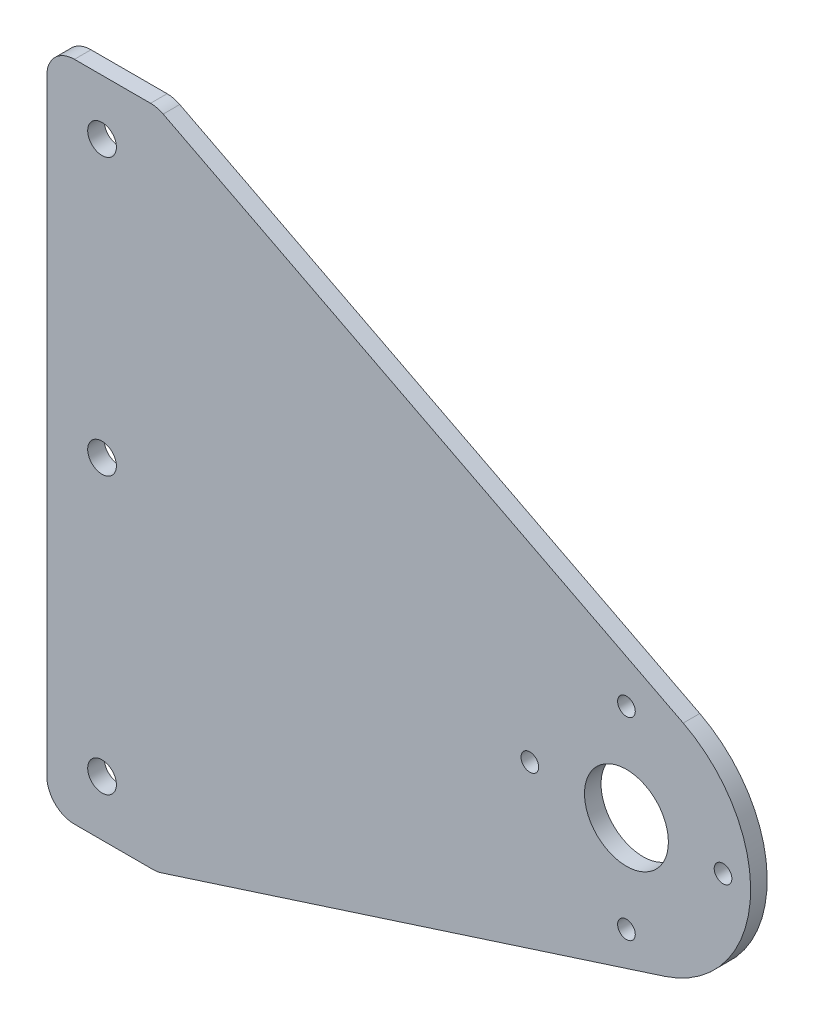
SolidWorks part; units mm, degrees
ref_plane "正面" through (0, 0, 0) normal (0, 0, 1) x (1, 0, 0)
ref_plane "平面" through (0, 0, 0) normal (0, 1, 0) x (1, 0, 0)
ref_plane "右側面" through (0, 0, 0) normal (1, 0, 0) x (0, 0, -1)
sketch "ｽｹｯﾁ2" plane through (0, 0, 0) normal (0, 0, 1) x (1, 0, 0)
  line L0 (17.5, 0) -> (-17.5, 0) construction
  line L1 (0, -17.5) -> (0, 17.5) construction
  line L2 (0, 0) -> (-85, 9) construction
  line L3 (-95, -41) -> (-95, 9) construction
  line L4 (-95, 9) -> (-95, 59) construction
  line L5 (-105, 69) -> (-105, -51)
  line L6 (-105, -51) -> (-85, -51)
  line L7 (-105, 69) -> (-85, 69)
  line L8 (-85, 69) -> (-85, -51) construction
  line L9 (-85, 69) -> (10.2878, 20.0103)
  line L10 (-85, -51) -> (6.8947, -21.4176)
  line L11 (-105, 9) -> (-85, 9) construction
  line L12 (0, -22.5) -> (-105, -22.5) construction
  line L13 (-105, -22.5) -> (-105, -51) construction
  line L14 (0, -76) -> (-105, -76) construction
  line L15 (-105, -51) -> (-105, -76) construction
  circle A0 centre (0, 0) radius 7.6
  circle A1 centre (0, 17.5) radius 1.6
  circle A2 centre (17.5, 0) radius 1.6
  circle A3 centre (0, -17.5) radius 1.6
  circle A4 centre (-17.5, 0) radius 1.6
  circle A5 centre (-95, 9) radius 2.6
  circle A6 centre (-95, 59) radius 2.6
  circle A7 centre (-95, -41) radius 2.6
  arc A8 (6.8947, -21.4176) -> (10.2878, 20.0103) centre (0, 0) ccw
  circle A9 centre (0, 0) radius 76 construction
  point P6 (0, 0)
  point P9 (0, 0)
  point P29 (-95, 9)
  dimension "D1" = 15.2
  dimension "D2" = 3.2
  dimension "D3" = 5.2
  dimension "D4" = 50
  dimension "D5" = 50
  dimension "D8" = 22.5
  dimension "D9" = 20
  dimension "D11" = 10
  dimension "D12" = 152
  dimension "D13" = 105
  dimension "D6" = 90
  dimension "D7" = 35
  dimension "D10" = 10
  dimension "D14" = 25
extrude "ﾎﾞｽ - 押し出し1" add sketch "ｽｹｯﾁ2" along normal blind 3
fillet "ﾌｨﾚｯﾄ3" radius 5 4 edges at (-85, 69, 1.5) (-85, -51, 1.5) (-105, -51, 1.5) (-105, 69, 1.5)
